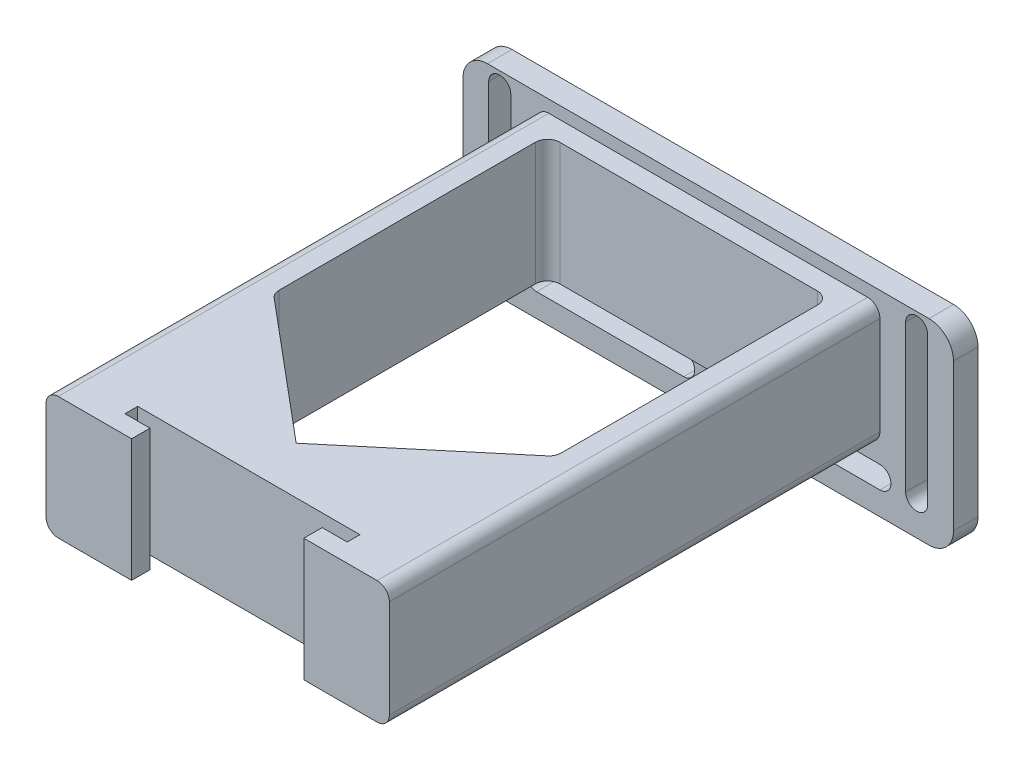
SolidWorks part; units mm, degrees
ref_plane "Front Plane" through (0, 0, 0) normal (0, 0, 1) x (1, 0, 0)
ref_plane "Top Plane" through (0, 0, 0) normal (0, 1, 0) x (1, 0, 0)
ref_plane "Right Plane" through (0, 0, 0) normal (1, 0, 0) x (0, 0, -1)
sketch "Sketch1" plane through (0, 0, 0) normal (0, 0, 1) x (1, 0, 0)
  line L1 (50, -20) -> (-50, -20)
  line L2 (50, -20) -> (50, 20)
  line L3 (50, 20) -> (-50, 20)
  line L4 (-50, -20) -> (-50, 20)
  line L5 (50, -20) -> (-50, 20) construction
  line L6 (50, 20) -> (-50, -20) construction
  point P0 (0, 0)
  dimension "D1" = 40
  dimension "D2" = 100
extrude "Boss-Extrude1" add sketch "Sketch1" along normal blind 5
sketch "Sketch2" plane through (0, 0, 5) normal (0, 0, 1) x (1, 0, 0)
  line L0 (-42.5, 17) -> (-42.5, -13) construction
  line L1 (-40.25, 17) -> (-40.25, -13)
  line L2 (-35, -13) -> (-5, -13) construction
  line L3 (-44.75, 17) -> (-44.75, -13)
  line L7 (42.5, 17) -> (42.5, -13) construction
  line L8 (44.75, 17) -> (44.75, -13)
  line L9 (40.25, 17) -> (40.25, -13)
  line L11 (5, -13) -> (35, -13) construction
  line L12 (5, -10.75) -> (35, -10.75)
  line L13 (5, -15.25) -> (35, -15.25)
  line L14 (-50, -20) -> (50, -20) construction
  line L15 (-50, 20) -> (-50, -20) construction
  line L16 (50, -20) -> (50, 20) construction
  line L17 (-35, -10.75) -> (-5, -10.75)
  line L18 (-35, -15.25) -> (-5, -15.25)
  arc A8 (-40.25, 17) -> (-44.75, 17) centre (-42.5, 17) ccw
  arc A9 (-44.75, -13) -> (-40.25, -13) centre (-42.5, -13) ccw
  arc A10 (44.75, 17) -> (40.25, 17) centre (42.5, 17) ccw
  arc A11 (40.25, -13) -> (44.75, -13) centre (42.5, -13) ccw
  arc A14 (5, -10.75) -> (5, -15.25) centre (5, -13) ccw
  arc A15 (35, -15.25) -> (35, -10.75) centre (35, -13) ccw
  arc A16 (-35, -10.75) -> (-35, -15.25) centre (-35, -13) ccw
  arc A17 (-5, -15.25) -> (-5, -10.75) centre (-5, -13) ccw
  point P2 (-42.5, 2)
  point P7 (-20, -13)
  point P10 (42.5, 2)
  point P21 (20, -13)
  dimension "D7" = 30
  dimension "D1" = 30
  dimension "D2" = 4.5
  dimension "D3" = 30
  dimension "D4" = 4.5
  dimension "D5" = 30
  dimension "D6" = 4.5
  dimension "D8" = 4.5
  dimension "D9" = 7
  dimension "D10" = 7
  dimension "D11" = 7.5
  dimension "D12" = 7.5
  dimension "D13" = 7.5
  dimension "D14" = 7.5
extrude "Cut-Extrude1" cut sketch "Sketch2" against normal blind 5 contours L1 A9 L3 A8
extrude "Cut-Extrude2" cut sketch "Sketch2<3>" against normal blind 5 contours L17 A17 L18 A16
sketch "Sketch2<3>" plane through (0, 0, 5) normal (0, 0, 1) x (1, 0, 0) same geometry as "Sketch2"
extrude "Cut-Extrude3" cut sketch "Sketch2<4>" against normal blind 5 contours L12 A15 L13 A14
sketch "Sketch2<4>" plane through (0, 0, 5) normal (0, 0, 1) x (1, 0, 0) same geometry as "Sketch2"
extrude "Cut-Extrude4" cut sketch "Sketch2<5>" against normal blind 5 contours L9 A11 L8 A10
sketch "Sketch2<5>" plane through (0, 0, 5) normal (0, 0, 1) x (1, 0, 0) same geometry as "Sketch2"
sketch "Sketch3" plane through (0, 0, 5) normal (0, 0, 1) x (1, 0, 0)
  line L0 (50, 20) -> (-50, 20) construction
  line L1 (35, -7.5) -> (-35, -7.5)
  line L2 (35, -7.5) -> (35, 17.5)
  line L3 (35, 17.5) -> (-35, 17.5)
  line L4 (-35, -7.5) -> (-35, 17.5)
  line L5 (35, -7.5) -> (-35, 17.5) construction
  line L6 (35, 17.5) -> (-35, -7.5) construction
  point P0 (0, 5)
  point P8 (0, 20)
  dimension "D1" = 25
  dimension "D2" = 70
  dimension "D3" = 2.5
extrude "Boss-Extrude2" add sketch "Sketch3" along normal blind 100
fillet "Fillet1" radius 5 4 edges at (-50, 20, 2.5) (50, 20, 2.5) (50, -20, 2.5) (-50, -20, 2.5)
fillet "Fillet2" radius 2.5 4 edges at (-35, 17.5, 55) (35, 17.5, 55) (35, -7.5, 55) (-35, -7.5, 55)
sketch "Sketch5" plane through (0, -7.5, 0) normal (0, -1, 0) x (1, 0, 0)
  line L4 (17.55, 101.25) -> (22.65, 101.25)
  line L5 (-22.65, 101.25) -> (-17.55, 101.25)
  line L7 (-22.65, 101.25) -> (-22.65, 98.65)
  line L8 (-22.65, 98.65) -> (22.65, 98.65)
  line L9 (22.65, 101.25) -> (22.65, 98.65)
  line L11 (17.55, 101.25) -> (17.55, 108.75)
  line L12 (17.55, 108.75) -> (-17.55, 108.75)
  line L13 (-17.55, 101.25) -> (-17.55, 108.75)
  line L14 (-32.5, 105) -> (32.5, 105) construction
  line L15 (-17.55, 105) -> (-35, 105) construction
  line L16 (17.55, 105) -> (35, 105) construction
  point P13 (-17.55, 105)
  dimension "D1" = 2.6
  dimension "D2" = 5.1
  dimension "D3" = 35.1
  dimension "D4" = 7.5
sketch "Sketch7" plane through (0, -7.5, 0) normal (0, -1, 0) x (1, 0, 0)
sketch "Sketch8" plane through (0, -7.5, 0) normal (0, -1, 0) x (1, 0, 0)
  line L0 (-28.75, 9) -> (28.75, 9)
  line L1 (28.75, 9) -> (28.75, 64.8759)
  line L2 (-28.75, 9) -> (-28.75, 64.8759)
  line L3 (-28.75, 64.8759) -> (0, 89)
  line L4 (0, 89) -> (28.75, 64.8759)
  line L5 (-32.5, 5) -> (32.5, 5) construction
  point P2 (0, 9)
  dimension "D1" = 50
  dimension "D2" = 4
  dimension "D3" = 80
  dimension "D4" = 57.5
extrude "Cut-Extrude8" cut sketch "Sketch8" against normal through all contours L2 L3 L4 L1 L0
fillet "Fillet3" radius 2.5 4 edges at (28.75, 5, 64.8759) (-28.75, 5, 64.8759) (28.75, 5, 9) (-28.75, 5, 9)
extrude "Cut-Extrude9" cut sketch "Sketch5" against normal through all contours L13 L12 L11 L4 L9 L8 L7 L5
